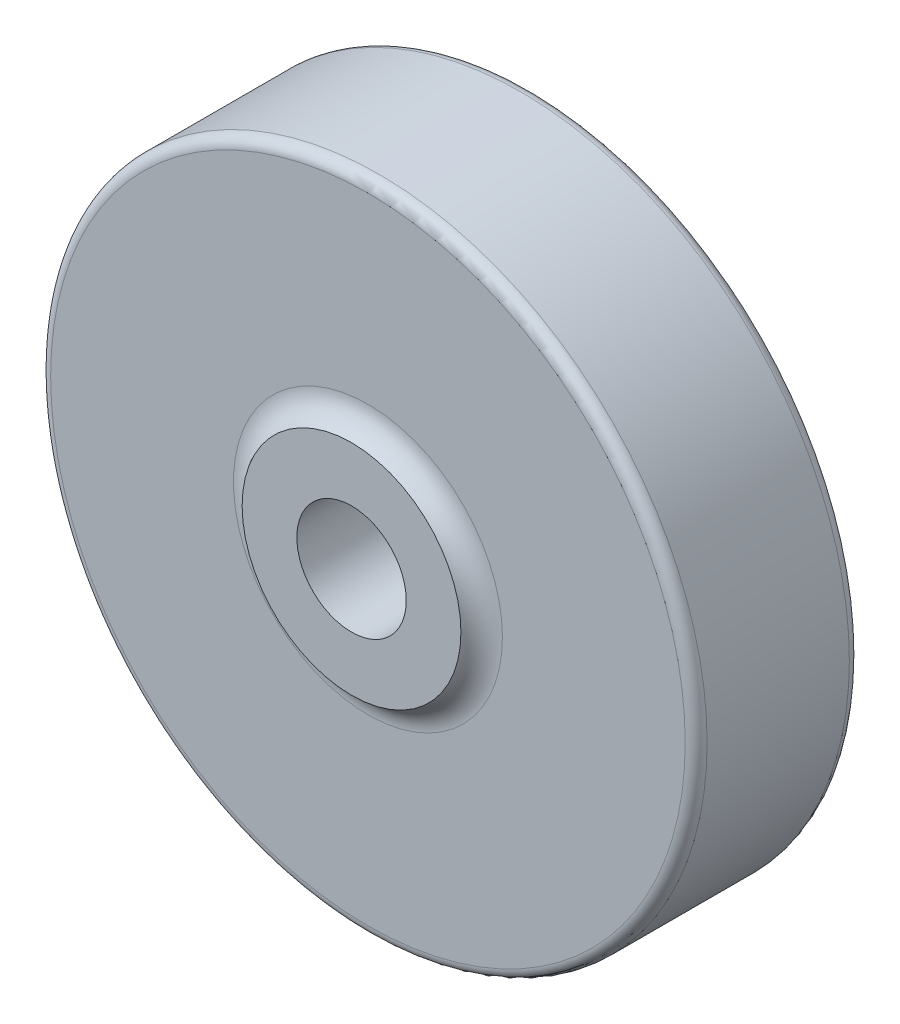
SolidWorks part; units mm, degrees
ref_plane "Front Plane" through (0, 0, 0) normal (0, 0, 1) x (1, 0, 0)
ref_plane "Top Plane" through (0, 0, 0) normal (0, 1, 0) x (1, 0, 0)
ref_plane "Right Plane" through (0, 0, 0) normal (1, 0, 0) x (0, 0, -1)
sketch "Sketch1" plane through (0, 0, 0) normal (0, 0, 1) x (1, 0, 0)
  circle A0 centre (0, 0) radius 60
  dimension "D1" = 120
extrude "Boss-Extrude1" add sketch "Sketch1" along normal blind 30
fillet "Fillet1" radius 2 2 edges at (60, 0, 30) (60, 0, 0)
sketch "Sketch6" plane through (0, 0, 30) normal (0, 0, 1) x (1, 0, 0)
  circle A1 centre (0, 0) radius 20
  dimension "D2" = 40
extrude "Boss-Extrude6" add sketch "Sketch6" along normal blind 3
sketch "Sketch9" plane through (0, 0, 33) normal (0, 0, 1) x (1, 0, 0)
  circle A0 centre (0, 0) radius 10
  dimension "D1" = 20
extrude "Cut-Extrude3" cut sketch "Sketch9" against normal through all
fillet "Fillet4" radius 5 1 edges at (20, 0, 30)
sketch "Sketch12" plane through (0, 0, 0) normal (0, 0, -1) x (-1, 0, 0)
  circle A0 centre (0, 0) radius 20
  dimension "D1" = 40
extrude "Boss-Extrude9" add sketch "Sketch12" along normal blind 3
fillet "Fillet7" radius 5 1 edges at (20, 0, 0)
sketch "Sketch14" plane through (0, 0, -3) normal (0, 0, -1) x (-1, 0, 0)
  circle A0 centre (0, 0) radius 10
  dimension "D1" = 20
extrude "Cut-Extrude5" cut sketch "Sketch14" against normal through all
